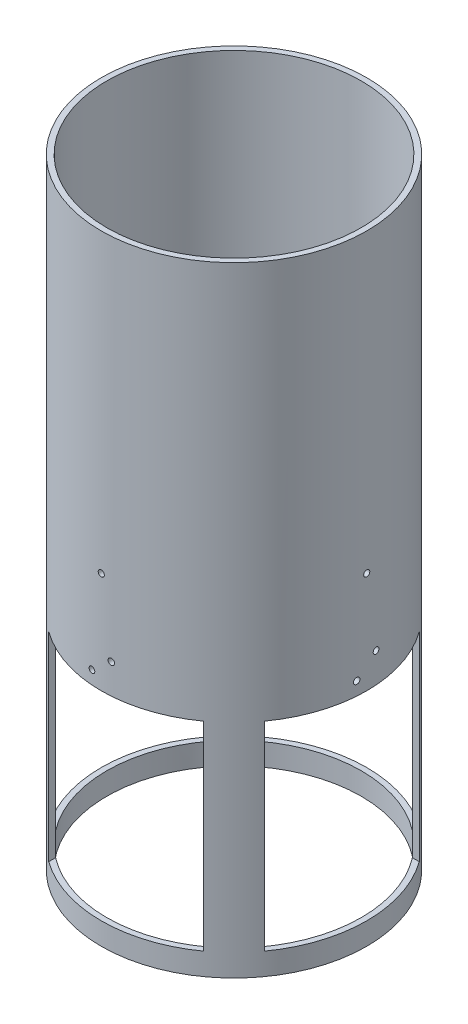
SolidWorks part; units mm, degrees
ref_plane "Front Plane" through (0, 0, 0) normal (0, 0, 1) x (1, 0, 0)
ref_plane "Top Plane" through (0, 0, 0) normal (0, 1, 0) x (1, 0, 0)
ref_plane "Right Plane" through (0, 0, 0) normal (1, 0, 0) x (0, 0, -1)
sketch "Sketch1" plane through (0, 0, 0) normal (0, 1, 0) x (1, 0, 0)
  circle A0 centre (0, 0) radius 76.2
  circle A1 centre (0, 0) radius 73.025
extrude "Boss-Extrude1" add sketch "Sketch1" along normal blind 355.6
sketch "Sketch5" plane through (0, 0, 0) normal (0, -1, 0) x (1, 0, 0)
  line L0 (0, 76.2) -> (0, -76.2) construction
  circle A0 centre (0, 0) radius 76.2 construction
ref_plane "Plane2" through (0, 0, -76.2) normal (0, 0, -1) x (-1, 0, 0)
sketch "Sketch6" plane through (0, 0, -76.2) normal (0, 0, -1) x (-1, 0, 0)
  line L0 (0, 355.6) -> (0, 127) construction
  line L1 (73.025, 355.6) -> (-73.025, 355.6) construction
  line L2 (-44.45, 127) -> (44.45, 127)
  line L13 (44.45, 127) -> (44.45, 12.7)
  line L16 (-44.45, 12.7) -> (44.45, 12.7)
  line L17 (-44.45, 127) -> (-44.45, 12.7)
  point P15 (0, 127)
extrude "Cut-Extrude6" cut sketch "Sketch6" against normal blind 20.574
pattern_circular "CirPattern9" count 4 over 360 about axis through (0, 0, 0) along (0, 1, 0) of "Cut-Extrude6"
sketch "Sketch7" plane through (0, 0, -76.2) normal (0, 0, -1) x (-1, 0, 0)
  line L0 (0, 0) -> (0, 127) construction
  line L1 (0, 127) -> (0, 134.62) construction
  line L2 (0, 127) -> (0, 144.145) construction
  line L3 (0, 127) -> (0, 185.42) construction
  line L4 (0, 134.62) -> (-5.5562, 134.62) construction
  line L5 (0, 144.145) -> (5.5562, 144.145) construction
  circle A2 centre (0, 185.42) radius 1.7526
  circle A3 centre (5.5562, 144.145) radius 1.7526
  circle A4 centre (-5.5562, 134.62) radius 1.7526
  point P6 (0, 134.62)
extrude "Cut-Extrude7" cut sketch "Sketch7" against normal blind 17.78 contours A4 | A3 | A2
pattern_circular "CirPattern10" count 4 over 360 about axis through (0, 355.6, 0) along (0, 1, 0) of "Cut-Extrude7"
